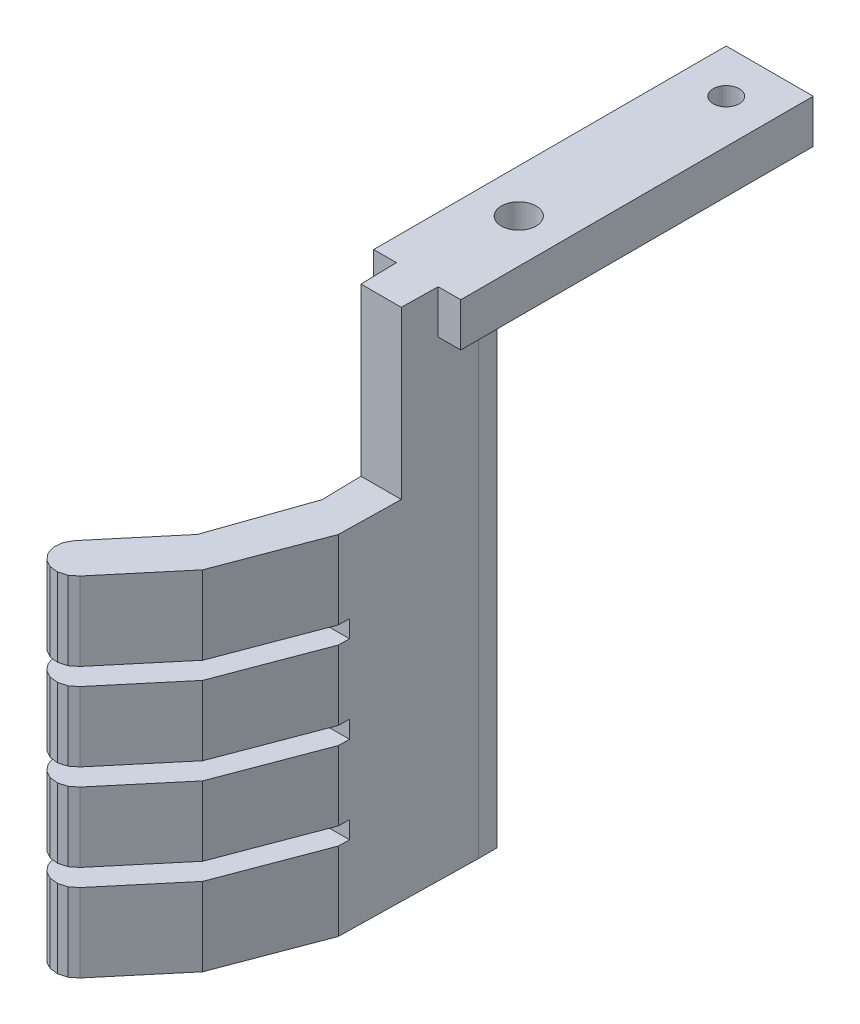
SolidWorks part; units mm, degrees
ref_plane "Front Plane" through (0, 0, 0) normal (0, 0, 1) x (1, 0, 0)
ref_plane "Top Plane" through (0, 0, 0) normal (0, 1, 0) x (1, 0, 0)
ref_plane "Right Plane" through (0, 0, 0) normal (1, 0, 0) x (0, 0, -1)
sketch "Sketch1" plane through (0, 0, 0) normal (0, 0, 1) x (1, 0, 0)
  line L0 (14.8, 20.475) -> (20.8, 20.475)
  line L1 (20.8, 20.475) -> (20.8, 23.475)
  line L2 (20.8, 23.475) -> (14.8, 23.475)
  line L3 (14.8, 23.475) -> (14.8, 20.475)
extrude "Boss-Extrude1" add sketch "Sketch1" along normal blind 24.3 from offset 7.2
sketch "Sketch2" plane through (0, 0, 0) normal (0, 1, 0) x (1, 0, 0)
  line L0 (16.3, -27.5) -> (16.3, -28.2355)
  line L1 (16.3, -28.2355) -> (16.4809, -36.7384)
  line L2 (16.4809, -36.7384) -> (14.2568, -43.1137)
  line L3 (14.2568, -43.1137) -> (10.4001, -47.7099)
  line L4 (10.4001, -47.7099) -> (10.1186, -48.2231)
  line L5 (10.1186, -48.2231) -> (10.0548, -48.8048)
  line L6 (10.0548, -48.8048) -> (10.2186, -49.3667)
  line L7 (10.2186, -49.3667) -> (10.585, -49.8232)
  line L8 (10.585, -49.8232) -> (11.0981, -50.1047)
  line L9 (11.0981, -50.1047) -> (11.6799, -50.1684)
  line L10 (11.6799, -50.1684) -> (12.2418, -50.0046)
  line L11 (12.2418, -50.0046) -> (12.6982, -49.6383)
  line L12 (12.6982, -49.6383) -> (16.5549, -45.042)
  line L13 (16.5549, -45.042) -> (19.1191, -38.2616)
  line L14 (19.1191, -38.2616) -> (19.3, -28.7645)
  line L15 (19.3, -28.7645) -> (19.3, -27.5)
  line L16 (19.3, -27.5) -> (16.3, -27.5)
extrude "Boss-Extrude2" add sketch "Sketch2" along normal blind 35.475 from offset 12 offset against normal yes
sketch "Sketch3" plane through (0, 0, 0) normal (0, 1, 0) x (1, 0, 0)
  circle A0 centre (17.8, -24.5) radius 1.2
  circle A1 centre (17.8, -10.2) radius 0.9
extrude "Cut-Extrude1" cut sketch "Sketch3" against normal through all and the other way through all
sketch "Sketch4" plane through (0, 0, 0) normal (1, 0, 0) x (0, 0, -1)
  line L0 (-37.5, -6.6) -> (-37.5, -5.4)
  line L1 (-37.5, -5.4) -> (-80, -5.4)
  line L2 (-80, -5.4) -> (-80, -6.6)
  line L3 (-80, -6.6) -> (-37.5, -6.6)
  line L4 (-37.5, -0.6) -> (-37.5, 0.6)
  line L5 (-37.5, 0.6) -> (-80, 0.6)
  line L6 (-80, 0.6) -> (-80, -0.6)
  line L7 (-80, -0.6) -> (-37.5, -0.6)
  line L8 (-37.5, 5.4) -> (-37.5, 6.6)
  line L9 (-37.5, 6.6) -> (-80, 6.6)
  line L10 (-80, 6.6) -> (-80, 5.4)
  line L11 (-80, 5.4) -> (-37.5, 5.4)
  line L12 (-34, 12) -> (-34, 24.475)
  line L13 (-34, 24.475) -> (-80, 24.475)
  line L14 (-80, 24.475) -> (-80, 12)
  line L15 (-80, 12) -> (-34, 12)
extrude "Cut-Extrude2" cut sketch "Sketch4" against normal through all and the other way through all
